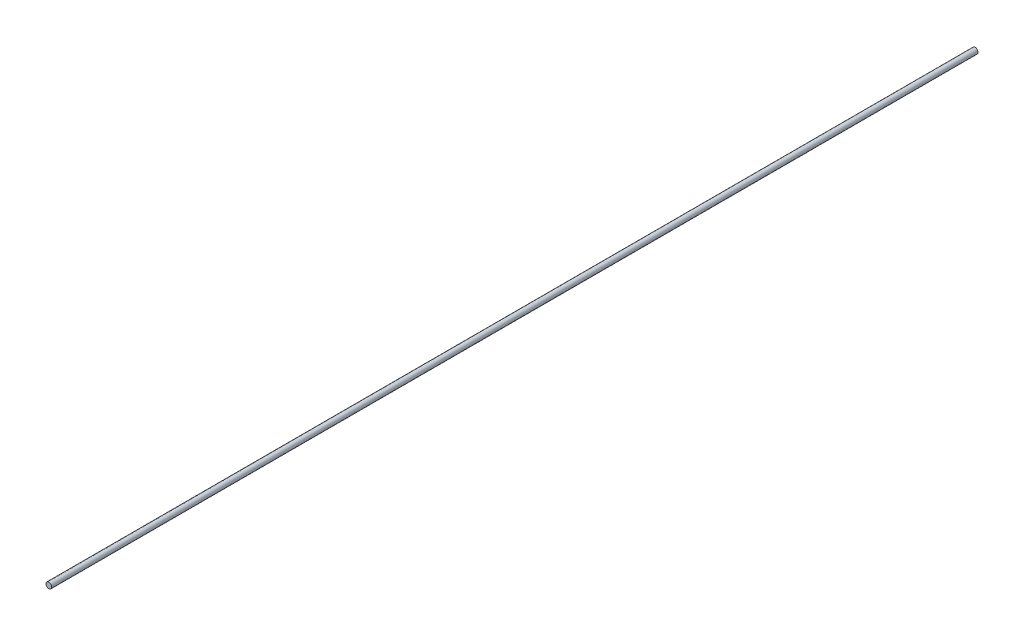
SolidWorks part; units mm, degrees
ref_plane "Front Plane" through (0, 0, 0) normal (0, 0, 1) x (1, 0, 0)
ref_plane "Top Plane" through (0, 0, 0) normal (0, 1, 0) x (1, 0, 0)
ref_plane "Right Plane" through (0, 0, 0) normal (1, 0, 0) x (0, 0, -1)
sketch "Sketch1" plane through (0, 0, 0) normal (0, 0, 1) x (1, 0, 0)
  circle A0 centre (0, 0) radius 2.5
extrude "Rod" add sketch "Sketch1" along normal blind 814
